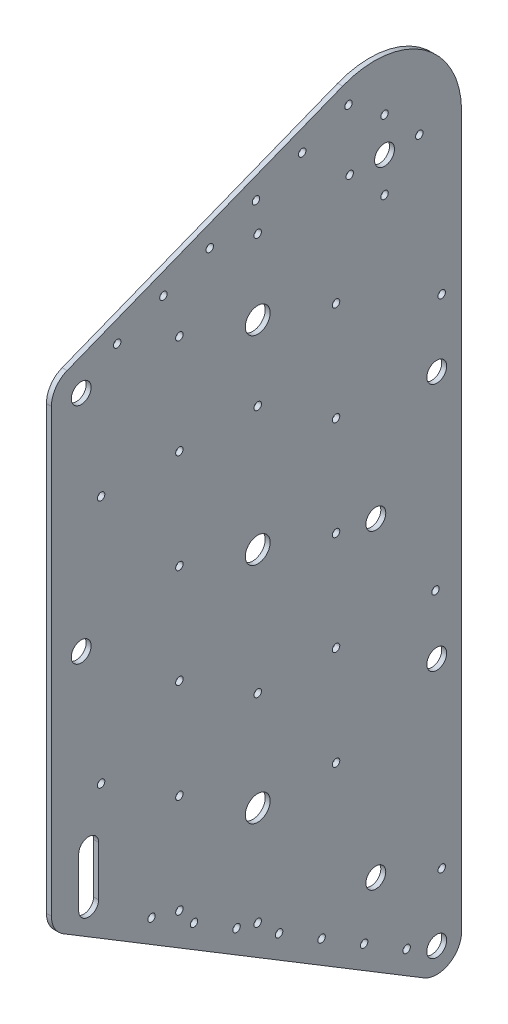
SolidWorks part; units mm, degrees
material "6061 Alloy"
ref_plane "Front Plane" through (0, 0, 0) normal (0, 0, 1) x (1, 0, 0)
ref_plane "Top Plane" through (0, 0, 0) normal (0, 1, 0) x (1, 0, 0)
ref_plane "Right Plane" through (0, 0, 0) normal (1, 0, 0) x (0, 0, -1)
sketch "Sketch2" plane through (0, 0, 0) normal (-1, 0, 0) x (0, 1, 0)
  line L0 (0, 0) -> (65, 165)
  line L1 (65, 165) -> (-290, 165)
  line L2 (-290, 165) -> (-190, 0)
  line L3 (-90.75, 0) -> (90.75, 0) construction
  line L4 (-190, 0) -> (0, 0)
  dimension "D1" = 355
  dimension "D2" = 190
  dimension "D3" = 165
  dimension "D4" = 65
extrude "Boss-Extrude1" add sketch "Sketch2" along normal blind 2
fillet "Fillet1" radius 10 3 edges at (-1, -190, 0) (-1, -290, -165) (-1, 0, 0)
sketch "Sketch3" plane through (-2, 0, 0) normal (-1, 0, 0) x (0, 1, 0)
  line L0 (-192.1703, 15) -> (-192.1703, 3.3924) construction
  line L1 (65, 165) -> (-272.2462, 165) construction
  line L2 (-280.7982, 149.817) -> (-192.9194, 4.817) construction
  line L3 (2.4955, 6.3348) -> (65, 165) construction
  line L4 (-164.1703, 15) -> (-164.1703, 3.3924) construction
  line L5 (-1.1, 0) -> (1.1, 0) construction
  line L6 (-261.9073, 134.0821) -> (-194.8085, 23.369) construction
  line L7 (-4.3733, 10.7251) -> (45.6685, 137.7543) construction
  line L8 (-102.1703, 12) -> (-102.1703, 4.9013) construction
  line L9 (-188.1703, 11) -> (-168.1703, 11)
  line L10 (-168.1703, 19) -> (-188.1703, 19)
  line L11 (-172.2462, 151) -> (-162.3574, 151) construction
  circle A0 centre (-272.2462, 155) radius 10 construction
  circle A1 centre (-228.1703, 83) radius 1.5
  circle A2 centre (-246.2462, 157) radius 1.5
  circle A3 centre (-46.2462, 157) radius 1.5
  circle A4 centre (11.8297, 83) radius 1.5
  circle A5 centre (13.8297, 134) radius 14 construction
  circle A6 centre (13.8297, 148) radius 1.5
  circle A7 centre (27.8297, 134) radius 1.5
  circle A8 centre (13.8297, 120) radius 1.5
  circle A9 centre (-0.1703, 134) radius 1.5
  arc A10 (-188.1703, 19) -> (-188.1703, 11) centre (-188.1703, 15) ccw
  arc A11 (-168.1703, 11) -> (-168.1703, 19) centre (-168.1703, 15) ccw
  circle A42 centre (-272.2462, 155) radius 4
  circle A43 centre (-172.2462, 155) radius 4
  circle A44 centre (13.8297, 134) radius 4
  circle A45 centre (-236.1703, 130.5) radius 4
  circle A46 centre (-111.1703, 130.5) radius 4
  circle A47 centre (-18.1703, 83) radius 5
  circle A48 centre (-188.1703, 83) radius 5
  circle A49 centre (-98.1703, 83) radius 5
  circle A50 centre (-205.05, 40.2675) radius 1.5
  circle A51 centre (-208.1703, 51.5) radius 1.5
  circle A52 centre (-225.7821, 74.4754) radius 1.5
  circle A53 centre (-236.1481, 91.5794) radius 1.5
  circle A54 centre (-246.5141, 108.6833) radius 1.5
  circle A55 centre (-256.8802, 125.7873) radius 1.5
  circle A56 centre (-267.2462, 142.8912) radius 1.5
  circle A57 centre (1.8297, 26.4713) radius 1.5
  circle A58 centre (9.1602, 45.0795) radius 1.5
  circle A59 centre (16.4907, 63.6876) radius 1.5
  circle A60 centre (23.8212, 82.2958) radius 1.5
  circle A61 centre (31.1517, 100.904) radius 1.5
  circle A62 centre (38.4822, 119.5121) radius 1.5
  circle A63 centre (-72.2462, 155) radius 4
  circle A64 centre (-148.1703, 154.5) radius 1.5
  circle A65 centre (-188.1703, 114.5) radius 1.5
  circle A66 centre (-148.1703, 114.5) radius 1.5
  circle A67 centre (-108.1703, 114.5) radius 1.5
  circle A68 centre (-68.1703, 114.5) radius 1.5
  circle A69 centre (-28.1703, 114.5) radius 1.5
  circle A70 centre (-148.1703, 83) radius 1.5
  circle A71 centre (-215.416, 57.3715) radius 1.5
  circle A72 centre (-168.1703, 51.5) radius 1.5
  circle A73 centre (-8.1703, 51.5) radius 1.5
  circle A74 centre (-128.1703, 51.5) radius 1.5
  circle A75 centre (-88.1703, 51.5) radius 1.5
  circle A76 centre (-48.1703, 83) radius 1.5
  circle A77 centre (-48.1703, 51.5) radius 1.5
  circle A78 centre (-8.1703, 12) radius 4
  circle A79 centre (-148.1703, 20) radius 1.5
  circle A80 centre (-98.1703, 12) radius 4
  circle A81 centre (-48.1703, 20) radius 1.5
  dimension "D1" = 3
  dimension "D2" = 8
  dimension "D3" = 20
  dimension "D4" = 20
  dimension "D6" = 20
  dimension "D7" = 20
  dimension "D8" = 20
  dimension "D9" = 8
  dimension "D10" = 5
  dimension "D11" = 20
  dimension "D12" = 12
  dimension "D13" = 31.5
  dimension "D14" = 31.5
  dimension "D15" = 31.5
  dimension "D16" = 40
  dimension "D17" = 40
  dimension "D18" = 40
  dimension "D19" = 40
  dimension "D20" = 40
  dimension "D21" = 40
  dimension "D22" = 12
  dimension "D24" = 40
  dimension "D25" = 90
  dimension "D26" = 80
  dimension "D27" = 50
  dimension "D28" = 10
  dimension "D29" = 40
  dimension "D30" = 40
  dimension "D31" = 40
  dimension "D32" = 40
  dimension "D33" = 3
  dimension "D34" = 16
  dimension "D35" = 125
  dimension "D37" = 8
  dimension "D38" = 10
  dimension "D39" = 20
  dimension "D40" = 20
  dimension "D41" = 20
  dimension "D42" = 20
  dimension "D43" = 20
  dimension "D44" = 100
  dimension "D45" = 100
  dimension "D46" = 40
  dimension "D47" = 30
  dimension "D48" = 8
  dimension "D5" = 20
  dimension "D23" = 90
  dimension "D36" = 125
  dimension "D49" = 26
  dimension "D50" = 200
  dimension "D51" = 3
  dimension "D52" = 28
  dimension "D56" = 21
  dimension "D53" = 28
  dimension "D54" = 62
  dimension "D55" = 132
extrude "Cut-Extrude1" cut sketch "Sketch3" against normal blind 2
fillet "Fillet2" radius 35 1 edges at (-1, 65, -165)
